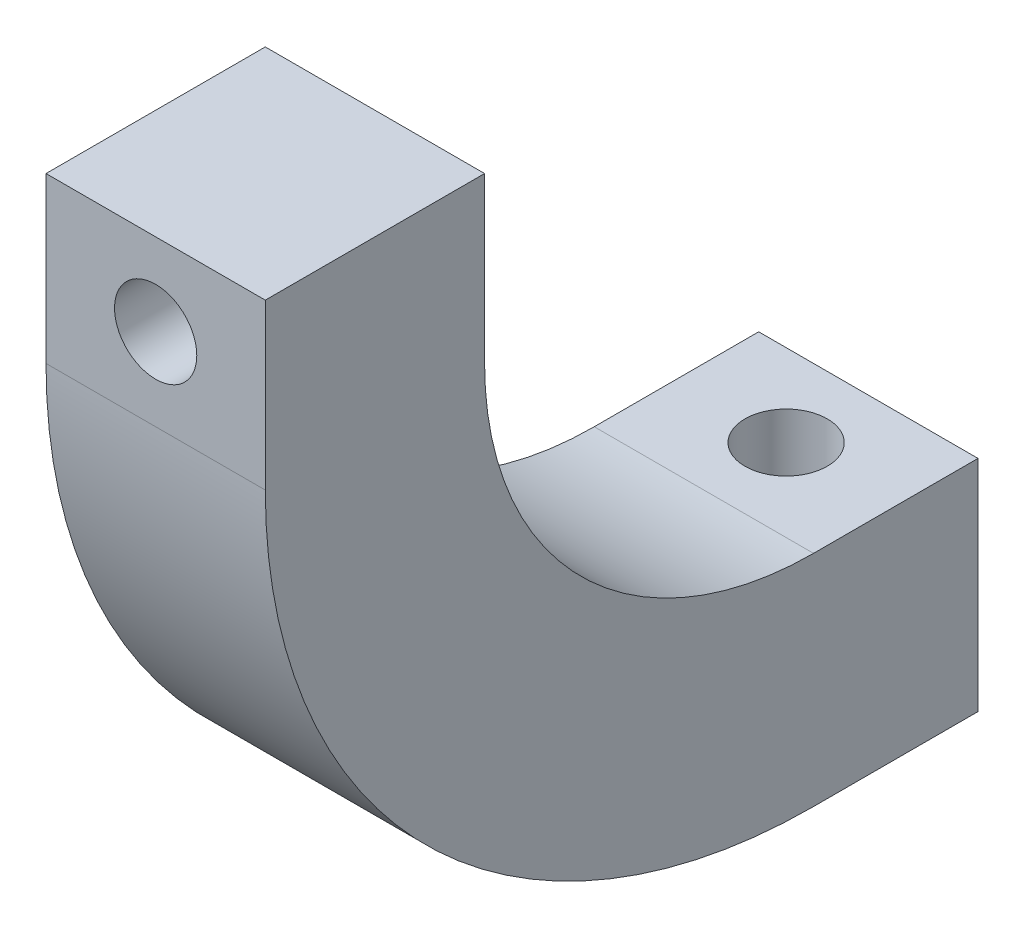
SolidWorks part; units mm, degrees
ref_plane "Front Plane" through (0, 0, 0) normal (0, 0, 1) x (1, 0, 0)
ref_plane "Top Plane" through (0, 0, 0) normal (0, 1, 0) x (1, 0, 0)
ref_plane "Right Plane" through (0, 0, 0) normal (1, 0, 0) x (0, 0, -1)
ref_axis "Z" through (0, 0, 22.75) along (0, 0, -1)
sketch "Sketch4" plane through (0, 0, 0) normal (0, 0, 1) x (1, 0, 0)
  circle A0 centre (0, 0) radius 14 construction
  dimension "D1" = 28
sketch "Sketch5" plane through (0, 0, 0) normal (1, 0, 0) x (0, 0, -1)
  line L0 (-15, 3) -> (-15, 0)
  line L1 (-15, 0) -> (-15, -3)
  line L2 (-23, -3) -> (-23, 3)
  line L6 (-23, 3) -> (-15, 3)
  line L12 (-22.75, 0) -> (-13.0351, 0) construction
  line L13 (0, 0) -> (-14.9091, -14.9091) construction
  line L14 (0, 0) -> (7.0065, 0) construction
  line L15 (0, -15) -> (-3, -15)
  line L16 (3, -15) -> (0, -15)
  line L17 (-3, -23) -> (3, -23)
  line L18 (3, -23) -> (3, -15)
  circle A0 centre (0, 0) radius 14 construction
  arc A1 (-15, -3) -> (-3, -15) centre (-3, -3) ccw
  arc A2 (-23, -3) -> (-3, -23) centre (-3, -3) ccw
  point P2 (9.4307, -21)
  point P4 (0, -2.1363)
  point P20 (-20.5214, -4.6985)
  point P22 (-36.7289, 3)
  dimension "D1" = 28
  dimension "D4" = 3
  dimension "D2" = 45
  dimension "D3" = 8
  dimension "D5" = 15
sketch "Sketch6" plane through (0, 0, 0) normal (0, 1, 0) x (1, 0, 0)
  circle A0 centre (0, 0) radius 14 construction
  dimension "D1" = 28
extrude "Boss-Extrude1" add sketch "Sketch5" along normal blind 4 and the other way blind 4
sketch "Sketch7" plane through (0, 0, 0) normal (0, 0, 1) x (1, 0, 0)
  circle A0 centre (0, 0) radius 1.5
  dimension "D1" = 3
extrude "Cut-Extrude1" cut sketch "Sketch7" along normal through all
sketch "Sketch8" plane through (0, 0, 0) normal (0, 1, 0) x (1, 0, 0)
  circle A0 centre (0, 0) radius 1.5
  dimension "D1" = 3
extrude "Cut-Extrude2" cut sketch "Sketch8" against normal through all
ref_axis "Y" through (0, -9.3489, 0) along (0, -1, 0)
equation "\"rbracket-width\"= \"L2Thickness\""
equation "\"EyeCaptureRadius\"= ( \"EyeDiameter\" + \"EyeClearance\" ) / 2"
equation "\"rbracket_planetocenterline_dist\"= \"BasePlaneDistance\""
equation "\"EyeDiameter\" = 28"
equation "\"BasePlaneDistance\" = 30"
equation "\"EyeClearance\" = 2"
equation "\"D1@Sketch4\"=\"EyeDiameter\""
equation "\"D1@Sketch6\"=\"EyeDiameter\""
equation "\"D1@Boss-Extrude1\"=\"rbracket-width\"/2"
equation "\"D2@Boss-Extrude1\"=\"rbracket-width\"/2"
equation "\"L2Thickness\" = 8"
equation "\"D3@Sketch5\"=\"L2Thickness\""
equation "\"D5@Sketch5\"=(\"EyeDiameter\"+\"EyeClearance\")/2"
